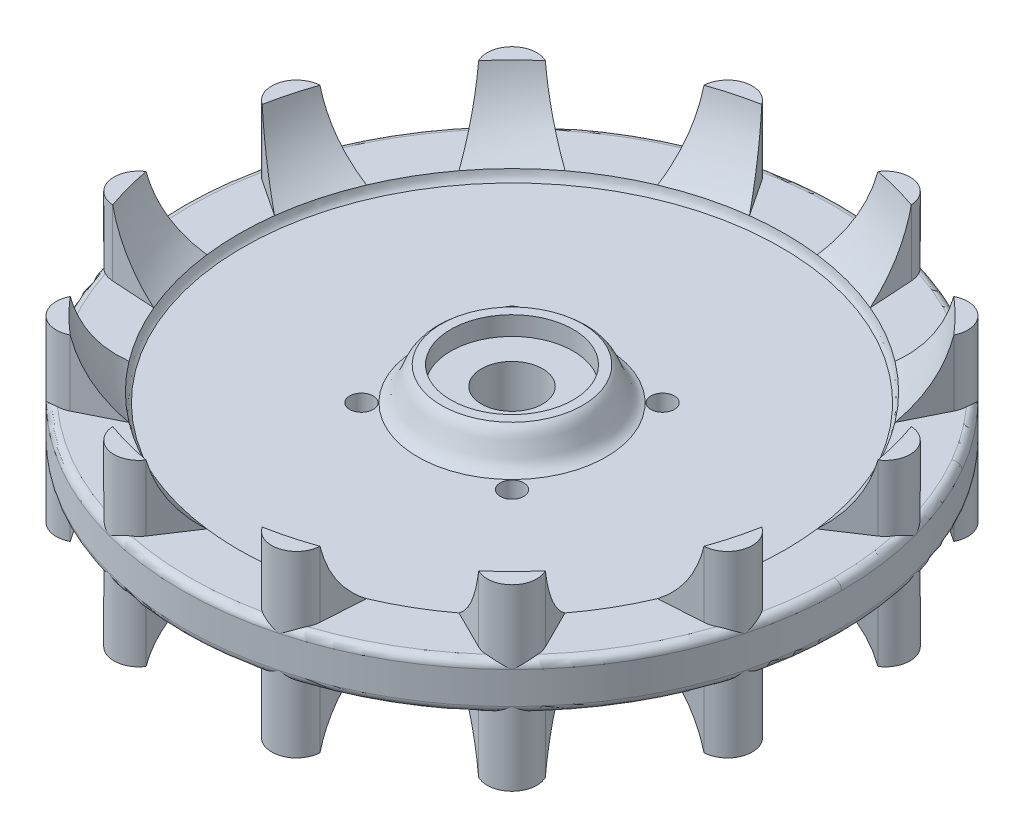
SolidWorks part; units mm, degrees
ref_plane "Front Plane" through (0, 0, 0) normal (0, 0, 1) x (1, 0, 0)
ref_plane "Top Plane" through (0, 0, 0) normal (0, 1, 0) x (1, 0, 0)
ref_plane "Right Plane" through (0, 0, 0) normal (1, 0, 0) x (0, 0, -1)
sketch "Sketch1" plane through (0, 0, 0) normal (0, 1, 0) x (1, 0, 0)
  line L0 (0, 0) -> (111.125, 0)
  line L1 (0, 0) -> (96.2371, 55.5625)
  arc A0 (111.125, 0) -> (96.2371, 55.5625) centre (0, 0) ccw
  dimension "D1" = 222.25
  dimension "D2" = 30
extrude "Boss-Extrude1" add sketch "Sketch1" along normal mid plane 15.875
fillet "Fillet2" radius 2.54 2 edges at (107.3385, 7.9375, -28.7613) (107.3385, -7.9375, -28.7613)
sketch "Sketch3" plane through (0, 7.9375, 0) normal (0, 1, 0) x (1, 0, 0)
  line L0 (0, 0) -> (107.3385, 28.7613) construction
  line L3 (84.8005, 35.8702) -> (99.7666, 34.9499)
  line L4 (91.3745, 11.3357) -> (103.8753, 19.6158)
  arc A0 (111.125, 0) -> (96.2371, 55.5625) centre (0, 0) ccw construction
  arc A1 (111.125, 0) -> (96.2371, 55.5625) centre (0, 0) ccw construction
  arc A2 (84.8005, 35.8702) -> (91.3745, 11.3357) centre (0, 0) cw
  arc A3 (99.7666, 34.9499) -> (103.8753, 19.6158) centre (99.2528, 26.5947) cw
  dimension "D1" = 92.075
  dimension "D2" = 15.875
  dimension "D3" = 25.4
extrude "Boss-Extrude3" add sketch "Sketch3" along normal blind 22.225 and the other way blind 38.1
pattern_circular "CirPattern8" count 12 over 360 about axis through (0, 7.9375, 0) along (0, -1, 0) of "Boss-Extrude1"
fillet "Fillet5" radius 2.54 2 edges at (-107.3385, -7.9375, 28.7613) (-107.3385, 7.9375, 28.7613)
pattern_circular "CirPattern9" count 12 over 360 about axis through (0, 7.9375, 0) along (0, -1, 0) of "Boss-Extrude3"
sketch "Sketch4" plane through (0, 0, 0) normal (1, 0, 0) x (0, 0, -1)
  line L0 (0, 4.7625) -> (-90.7661, 4.7625)
  line L1 (-91.3745, 30.1625) -> (-103.8753, 30.1625) construction
  line L2 (-91.3745, 30.1625) -> (-103.8753, 30.1625) construction
  line L3 (0, 7.9375) -> (0, 30.1625)
  line L5 (-92.202, 7.9375) -> (0, 7.9375) construction
  line L6 (0, 7.9375) -> (0, 4.7625)
  line L7 (0, 5.3975) -> (0, -5.3975) construction
  line L8 (-34.0198, 7.9375) -> (-72.2931, 7.9375) construction
  line L9 (-34.0198, 7.9375) -> (-72.2931, 7.9375) construction
  line L10 (0, 30.1625) -> (-105.664, 30.1625)
  spline S0 degree 2 poles (-105.664, 30.1625) (-102.6911, 16.6302) (-92.202, 7.9375) knots 0 0 0 1 1 1
  spline S1 degree 3 poles (-92.202, 7.9375) (-91.9702, 6.7822) (-91.8087, 5.5926) (-90.7661, 4.7625) knots 0 0 0 0 1 1 1 1
  point P11 (0, 6.35)
  dimension "D6" = 1.27
  dimension "D7" = 91.7112
  dimension "D2" = 92.202
  dimension "D3" = 3.175
  dimension "D4" = 105.664
  dimension "D5" = 5.9739
  dimension "D8" = 90.7661
  dimension "D9" = 14.0649
revolve "Cut-Revolve1" cut sketch "Sketch4" angle 360 about axis through (0, 7.9375, 0) along (0, -1, 0)
mirror "Mirror7" about plane through (0, 0, 0) normal (0, 1, 0) of "Cut-Revolve1"
sketch "Sketch5" plane through (0, 4.7625, 0) normal (0, 1, 0) x (1, 0, 0)
  circle A0 centre (0, 0) radius 10.3187
  dimension "D1" = 20.6375
extrude "Cut-Extrude1" cut sketch "Sketch5" against normal up to surface (9.525 mm away) up to face at (0, -4.7625, 90.7661)
sketch "Sketch7" plane through (0, 0, 0) normal (0, 1, 0) x (1, 0, 0)
  circle A0 centre (0, 0) radius 31.75
  circle A1 centre (0, 0) radius 10.3187 construction
  circle A2 centre (0, 0) radius 10.3187
  dimension "D1" = 63.5
extrude "Boss-Extrude4" add sketch "Sketch7" along normal mid plane 31.75
sketch "Sketch8" plane through (0, 15.875, 0) normal (0, 1, 0) x (1, 0, 0)
  circle A0 centre (0, 0) radius 20.6375
  circle A1 centre (0, 0) radius 10.3187
  dimension "D1" = 41.275
  dimension "D2" = 20.6375
extrude "Cut-Extrude2" cut sketch "Sketch8" against normal blind 6.35
sketch "Sketch9" plane through (0, 0, 0) normal (0, 0, 1) x (1, 0, 0)
  line L0 (20.6375, 15.875) -> (-20.6375, 15.875) construction
  line L1 (20.6375, 15.875) -> (-20.6375, 15.875) construction
  line L3 (31.75, 4.7625) -> (-31.75, 4.7625) construction
  line L4 (-10.3187, -15.875) -> (10.3187, -15.875) construction
  line L5 (-10.3187, -15.875) -> (10.3187, -15.875) construction
  line L6 (-31.75, -4.7625) -> (31.75, -4.7625) construction
  line L7 (-31.75, -4.7625) -> (31.75, -4.7625) construction
  line L8 (31.75, 4.7625) -> (-31.75, 4.7625) construction
  line L9 (20.6375, 15.875) -> (23.8125, 15.875) construction
  line L10 (31.75, 4.7625) -> (31.75, 15.875)
  line L11 (31.75, 15.875) -> (23.8125, 15.875)
  line L12 (19.05, -15.875) -> (31.75, -15.875)
  line L13 (31.75, -15.875) -> (31.75, -4.7625)
  spline S0 degree 3 poles (23.8125, 15.875) (27.9934, 13.1228) (26.3992, 6.5307) (31.75, 4.7625) knots 0 0 0 0 1 1 1 1
  spline S1 degree 3 poles (31.75, -4.7625) (29.1183, -5.8754) (25.9636, -9.3829) (23.6231, -13.6202) (21.1954, -15.3663) (19.05, -15.875) knots 0 0 0 0 0.499315 0.581239 1 1 1 1
  dimension "D11" = 12.7
  dimension "D1" = 3.175
  dimension "D2" = 2.0223
  dimension "D3" = 2.2217
  dimension "D4" = 2.992
  dimension "D5" = 3.473
  dimension "D6" = 2.8224
  dimension "D7" = 1.829
  dimension "D8" = 4.2781
  dimension "D9" = 5.692
  dimension "D10" = 8.7313
revolve "Cut-Revolve2" cut sketch "Sketch9" angle 360 about axis through (0, -33.9483, 0) along (0, 1, 0)
sketch "Sketch10" plane through (0, 0, 0) normal (0, 1, 0) x (1, 0, 0)
  line L0 (0, 0) -> (-72.4571, -72.4571) construction
  circle A0 centre (0, 0) radius 35.9156 construction
  circle A1 centre (-25.3962, -25.3962) radius 3.9688
  circle A2 centre (-25.3962, 25.3962) radius 3.9687
  circle A3 centre (25.3962, 25.3962) radius 3.9687
  circle A4 centre (25.3962, -25.3962) radius 3.9687
  point P22 (0, 0)
  dimension "D2" = 71.8312
  dimension "D1" = 7.9375
  dimension "D4" = 90
  dimension "D5" = 90
  dimension "D3" = 4
extrude "Cut-Extrude3" cut sketch "Sketch10" against normal up to surface and the other way up to surface up to face at (0, -4.7625, 90.7661) other way up to face at (0, 4.7625, 90.7661)
equation "\"0.5n\"=1.25"
